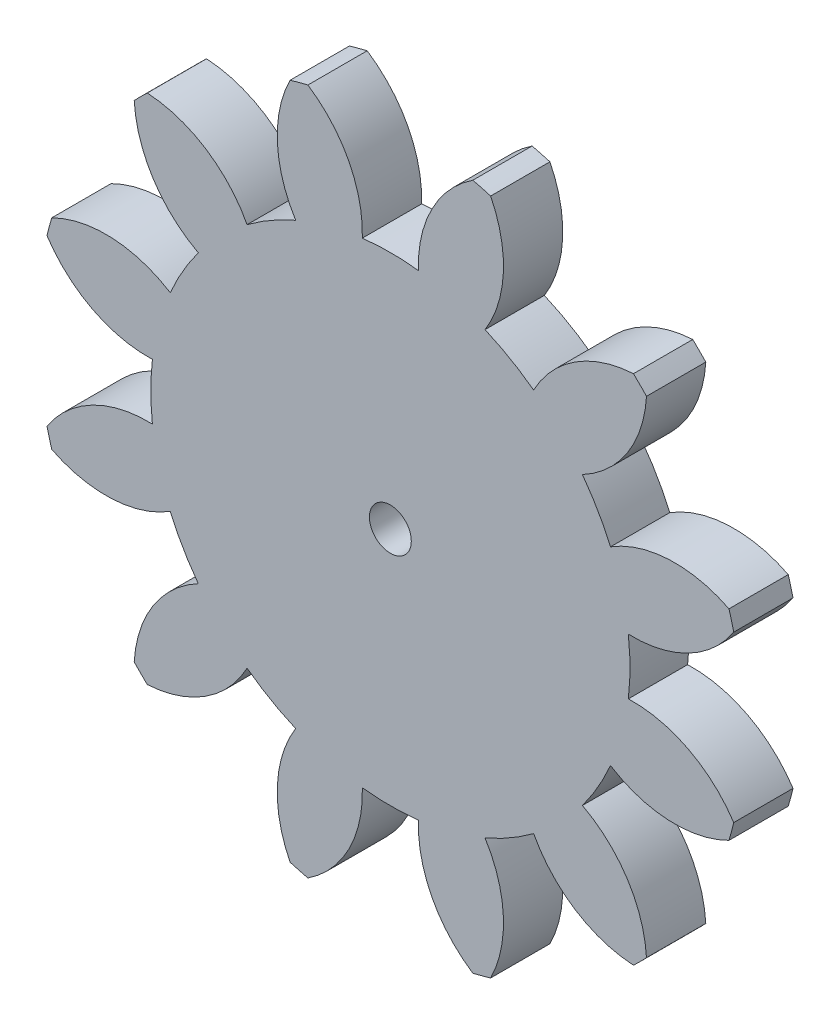
SolidWorks part; units mm, degrees
ref_plane "Front Plane" through (0, 0, 0) normal (0, 0, 1) x (1, 0, 0)
ref_plane "Top Plane" through (0, 0, 0) normal (0, 1, 0) x (1, 0, 0)
ref_plane "Right Plane" through (0, 0, 0) normal (1, 0, 0) x (0, 0, -1)
sketch "Sketch1" plane through (0, 0, 0) normal (0, 0, 1) x (1, 0, 0)
  arc A0 (31.0892, -0.0096) -> (27.1315, -2.5505) centre (31.371, -4.8013) ccw
  arc A1 (27.1315, -2.5505) -> (25.2056, -1.4386) centre (21.4517, -10.1644) ccw
  arc A2 (25.2056, -1.4386) -> (25.4272, 3.2593) centre (21.1366, 1.1075) ccw
  arc A3 (25.4272, 3.2593) -> (24.7206, 3.4487) centre (21.4517, -10.1644) ccw
  arc A4 (24.7206, 3.4487) -> (22.5636, -0.7307) centre (27.3606, -0.5602) ccw
  arc A5 (22.5636, -0.7307) -> (20.3398, -0.7307) centre (21.4517, -10.1644) ccw
  arc A6 (20.3398, -0.7307) -> (18.1828, 3.4487) centre (15.5428, -0.5602) ccw
  arc A7 (18.1828, 3.4487) -> (17.4762, 3.2593) centre (21.4517, -10.1644) ccw
  arc A8 (17.4762, 3.2593) -> (17.6978, -1.4386) centre (21.7669, 1.1075) ccw
  arc A9 (17.6978, -1.4386) -> (15.7719, -2.5505) centre (21.4517, -10.1644) ccw
  arc A10 (15.7719, -2.5505) -> (11.8142, -0.0096) centre (11.5324, -4.8013) ccw
  arc A11 (11.8142, -0.0096) -> (11.297, -0.5269) centre (21.4517, -10.1644) ccw
  arc A12 (11.297, -0.5269) -> (13.8378, -4.4846) centre (16.0887, -0.245) ccw
  arc A13 (13.8378, -4.4846) -> (12.7259, -6.4104) centre (21.4517, -10.1644) ccw
  arc A14 (12.7259, -6.4104) -> (8.028, -6.1888) centre (10.1798, -10.4795) ccw
  arc A15 (8.028, -6.1888) -> (7.8387, -6.8954) centre (21.4517, -10.1644) ccw
  arc A16 (7.8387, -6.8954) -> (12.018, -9.0524) centre (11.8475, -4.2555) ccw
  arc A17 (12.018, -9.0524) -> (12.018, -11.2763) centre (21.4517, -10.1644) ccw
  arc A18 (12.018, -11.2763) -> (7.8387, -13.4333) centre (11.8475, -16.0732) ccw
  arc A19 (7.8387, -13.4333) -> (8.028, -14.1399) centre (21.4517, -10.1644) ccw
  arc A20 (8.028, -14.1399) -> (12.7259, -13.9183) centre (10.1798, -9.8492) ccw
  arc A21 (12.7259, -13.9183) -> (13.8378, -15.8441) centre (21.4517, -10.1644) ccw
  arc A22 (13.8378, -15.8441) -> (11.297, -19.8018) centre (16.0887, -20.0837) ccw
  arc A23 (11.297, -19.8018) -> (11.8142, -20.3191) centre (21.4517, -10.1644) ccw
  arc A24 (11.8142, -20.3191) -> (15.7719, -17.7782) centre (11.5324, -15.5274) ccw
  arc A25 (15.7719, -17.7782) -> (17.6978, -18.8901) centre (21.4517, -10.1644) ccw
  arc A26 (17.6978, -18.8901) -> (17.4762, -23.588) centre (21.7669, -21.4363) ccw
  arc A27 (17.4762, -23.588) -> (18.1828, -23.7774) centre (21.4517, -10.1644) ccw
  arc A28 (18.1828, -23.7774) -> (20.3398, -19.5981) centre (15.5428, -19.7685) ccw
  arc A29 (20.3398, -19.5981) -> (22.5636, -19.5981) centre (21.4517, -10.1644) ccw
  arc A30 (22.5636, -19.5981) -> (24.7206, -23.7774) centre (27.3606, -19.7685) ccw
  arc A31 (24.7206, -23.7774) -> (25.4272, -23.588) centre (21.4517, -10.1644) ccw
  arc A32 (25.4272, -23.588) -> (25.2056, -18.8901) centre (21.1366, -21.4363) ccw
  arc A33 (25.2056, -18.8901) -> (27.1315, -17.7782) centre (21.4517, -10.1644) ccw
  arc A34 (27.1315, -17.7782) -> (31.0892, -20.3191) centre (31.371, -15.5274) ccw
  arc A35 (31.0892, -20.3191) -> (31.6064, -19.8018) centre (21.4517, -10.1644) ccw
  arc A36 (31.6064, -19.8018) -> (29.0656, -15.8441) centre (26.8147, -20.0837) ccw
  arc A37 (29.0656, -15.8441) -> (30.1775, -13.9183) centre (21.4517, -10.1644) ccw
  arc A38 (30.1775, -13.9183) -> (34.8754, -14.1399) centre (32.7236, -9.8492) ccw
  arc A39 (34.8754, -14.1399) -> (35.0647, -13.4333) centre (21.4517, -10.1644) ccw
  arc A40 (35.0647, -13.4333) -> (30.8854, -11.2763) centre (31.0559, -16.0732) ccw
  arc A41 (30.8854, -11.2763) -> (30.8854, -9.0524) centre (21.4517, -10.1644) ccw
  arc A42 (30.8854, -9.0524) -> (35.0647, -6.8954) centre (31.0559, -4.2555) ccw
  arc A43 (35.0647, -6.8954) -> (34.8754, -6.1888) centre (21.4517, -10.1644) ccw
  arc A44 (34.8754, -6.1888) -> (30.1775, -6.4104) centre (32.7236, -10.4795) ccw
  arc A45 (30.1775, -6.4104) -> (29.0656, -4.4846) centre (21.4517, -10.1644) ccw
  arc A46 (29.0656, -4.4846) -> (31.6064, -0.5269) centre (26.8147, -0.245) ccw
  arc A47 (31.6064, -0.5269) -> (31.0892, -0.0096) centre (21.4517, -10.1644) ccw
  circle A48 centre (21.4517, -10.1644) radius 0.83
  dimension "D1" = 1.66
extrude "Boss-Extrude1" add sketch "Sketch1" along normal blind 2.35
